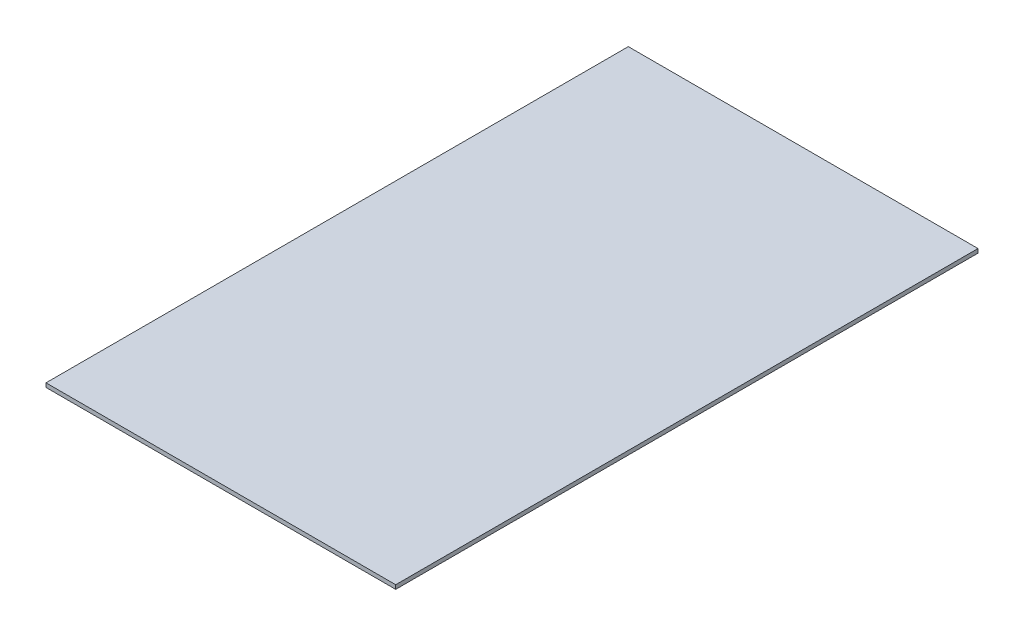
SolidWorks part; units mm, degrees
ref_plane "Front Plane" through (0, 0, 0) normal (0, 0, 1) x (1, 0, 0)
ref_plane "Top Plane" through (0, 0, 0) normal (0, 1, 0) x (1, 0, 0)
ref_plane "Right Plane" through (0, 0, 0) normal (1, 0, 0) x (0, 0, -1)
sketch "Sketch1" plane through (0, 0, 0) normal (0, 0, 1) x (1, 0, 0)
  line L1 (-137.2845, 1.5875) -> (137.2845, 1.5875)
  line L2 (-137.2845, 1.5875) -> (-137.2845, -1.5875)
  line L3 (-137.2845, -1.5875) -> (137.2845, -1.5875)
  line L4 (137.2845, 1.5875) -> (137.2845, -1.5875)
  line L5 (-137.2845, 1.5875) -> (137.2845, -1.5875) construction
  line L6 (-137.2845, -1.5875) -> (137.2845, 1.5875) construction
  point P0 (0, 0)
  dimension "D1" = 3.175
  dimension "D2" = 274.5689
extrude "Boss-Extrude1" add sketch "Sketch1" along normal blind 457.2 contours L1 L4 L3 L2
